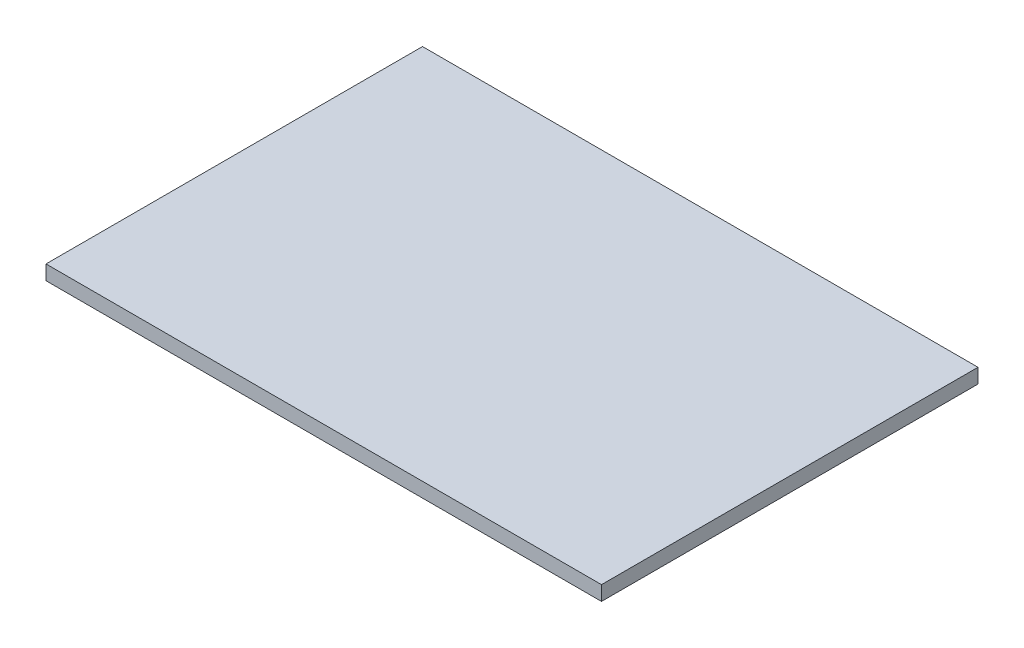
SolidWorks part; units mm, degrees
ref_plane "Front Plane" through (0, 0, 0) normal (0, 0, 1) x (1, 0, 0)
ref_plane "Top Plane" through (0, 0, 0) normal (0, 1, 0) x (1, 0, 0)
ref_plane "Right Plane" through (0, 0, 0) normal (1, 0, 0) x (0, 0, -1)
sketch "Sketch1" plane through (0, 0, 0) normal (0, 1, 0) x (1, 0, 0)
  line L1 (-45, 30.5) -> (45, 30.5)
  line L2 (-45, 30.5) -> (-45, -30.5)
  line L3 (-45, -30.5) -> (45, -30.5)
  line L4 (45, 30.5) -> (45, -30.5)
  line L5 (-45, 30.5) -> (45, -30.5) construction
  line L6 (-45, -30.5) -> (45, 30.5) construction
  point P0 (0, 0)
  dimension "D1" = 61
  dimension "D2" = 90
extrude "Boss-Extrude1" add sketch "Sketch1" along normal mid plane 2.36
